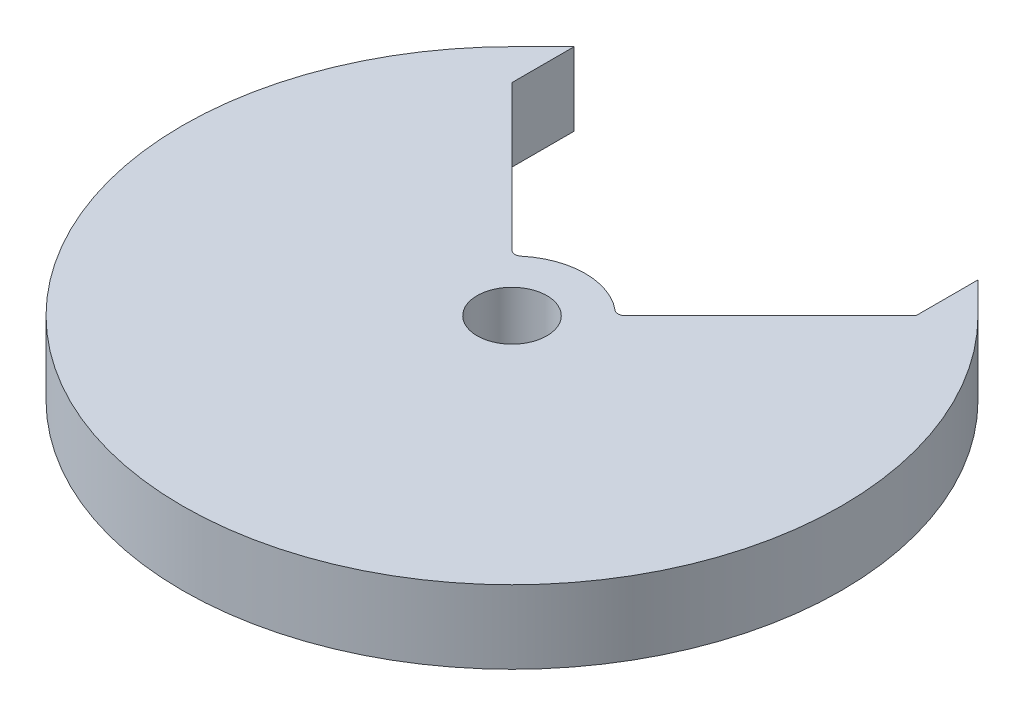
SolidWorks part; units mm, degrees
material "ABS"
ref_plane "Front Plane" through (0, 0, 0) normal (0, 0, 1) x (1, 0, 0)
ref_plane "Top Plane" through (0, 0, 0) normal (0, 1, 0) x (1, 0, 0)
ref_plane "Right Plane" through (0, 0, 0) normal (1, 0, 0) x (0, 0, -1)
sketch "Sketch1" plane through (0, 0, 0) normal (0, 1, 0) x (1, 0, 0)
  line L0 (-31.8198, 31.8198) -> (-7.0711, 7.0711)
  line L1 (7.0711, 7.0711) -> (31.8198, 31.8198)
  line L2 (0, 0) -> (0, 20) construction
  line L3 (0, 0) -> (-7.0711, 7.0711) construction
  line L4 (7.0711, 7.0711) -> (0, 0) construction
  arc A0 (-31.8198, 31.8198) -> (31.8198, 31.8198) centre (0, 0) ccw
  circle A1 centre (0, 0) radius 4.7625
  arc A2 (7.0711, 7.0711) -> (-7.0711, 7.0711) centre (0, 0) ccw
  dimension "D1" = 9.525
  dimension "D2" = 90
  dimension "D3" = 20
  dimension "D4" = 45
extrude "Boss-Extrude1" add sketch "Sketch1" along normal blind 10
fillet "Fillet1" radius 1 2 edges at (7.0711, 5, -7.0711) (-7.0711, 5, -7.0711)
sketch "Sketch2" plane through (0, 10, 0) normal (0, 1, 0) x (1, 0, 0)
  line L0 (4.0536, 2.5) -> (4.0536, -2.5)
  arc A0 (4.0536, -2.5) -> (4.0536, 2.5) centre (0, 0) ccw
  circle A1 centre (0, 0) radius 4.7625 construction
  dimension "D1" = 5
extrude "Shaft D" [suppressed] add sketch "Sketch2" against normal up to surface (10 mm away) up to face at (0, 0, -3.2457)
sketch "Sketch3" plane through (0, 10, 0) normal (0, 1, 0) x (1, 0, 0)
  line L0 (-31.8198, 31.8198) -> (-27.5772, 36.0624)
  line L1 (-27.5772, 36.0624) -> (-27.5772, 27.5772)
  line L2 (-7.746, 7.746) -> (-31.8198, 31.8198) construction
  line L3 (-27.5772, 27.5772) -> (-31.8198, 31.8198)
  line L4 (0, 0) -> (0, 30.6174) construction
  line L5 (27.5772, 27.5772) -> (31.8198, 31.8198)
  line L6 (27.5772, 36.0624) -> (27.5772, 27.5772)
  line L7 (31.8198, 31.8198) -> (27.5772, 36.0624)
  dimension "D1" = 6
extrude "Boss-Extrude2" add sketch "Sketch3" against normal up to surface (10 mm away) up to face at (0, 0, -3.2457)
